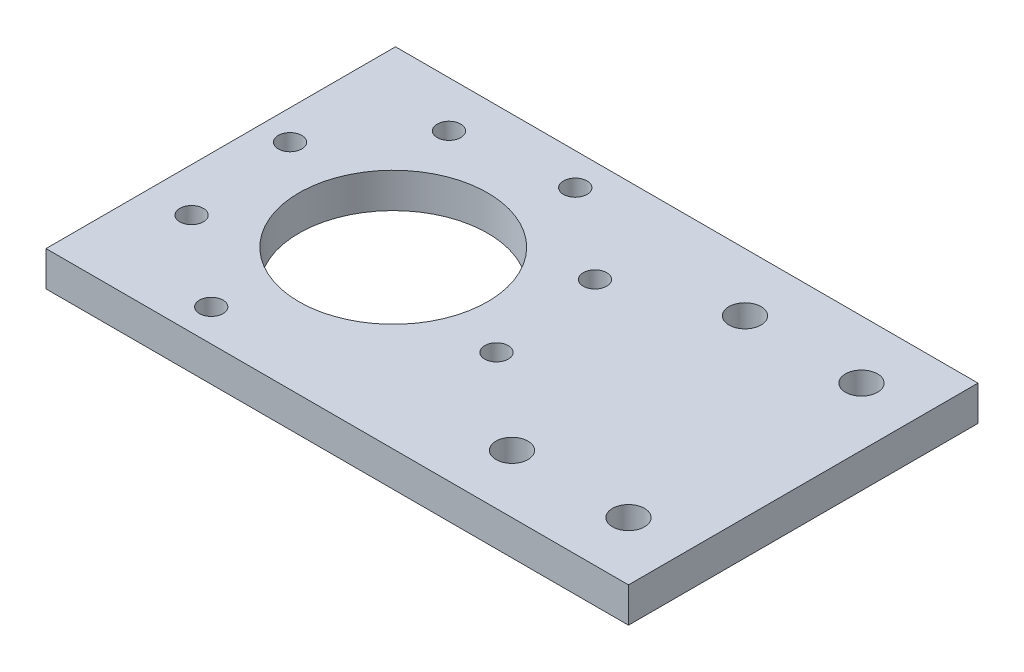
SolidWorks part; units mm, degrees
ref_plane "Front Plane" through (0, 0, 0) normal (0, 0, 1) x (1, 0, 0)
ref_plane "Top Plane" through (0, 0, 0) normal (0, 1, 0) x (1, 0, 0)
ref_plane "Right Plane" through (0, 0, 0) normal (1, 0, 0) x (0, 0, -1)
sketch "Sketch1" plane through (0, 0, 0) normal (0, 1, 0) x (1, 0, 0)
  line L1 (0, 0) -> (100, 0)
  line L2 (0, 0) -> (0, 60)
  line L3 (0, 60) -> (100, 60)
  line L4 (100, 0) -> (100, 60)
  dimension "D1" = 100
  dimension "D2" = 60
extrude "Boss-Extrude1" add sketch "Sketch1" along normal blind 6
sketch "Sketch2" plane through (0, 6, 0) normal (0, 1, 0) x (1, 0, 0)
  line L1 (100, 0) -> (100, 60) construction
  line L7 (100, 30) -> (0, 30) construction
  line L8 (0, 60) -> (0, 0) construction
  circle A0 centre (29.6153, 30) radius 16.1973
  circle A5 centre (70, 50) radius 2.75
  circle A6 centre (90, 50) radius 2.75
  circle A7 centre (70, 10) radius 2.75
  circle A8 centre (90, 10) radius 2.75
  point P7 (100, 30)
extrude "Cut-Extrude1" cut sketch "Sketch2" against normal blind 6
sketch "Sketch3" plane through (0, 0, 0) normal (0, -1, 0) x (1, 0, 0)
  circle A0 centre (54.0983, -23.2366) radius 2.0193 construction
  circle A1 centre (51.7099, -42.5296) radius 2.0193 construction
  circle A2 centre (36.3788, -54.483) radius 2.0193 construction
  circle A3 centre (17.0857, -52.0945) radius 2.0193 construction
  circle A4 centre (7.5208, -17.4704) radius 2.0193 construction
  circle A5 centre (22.8519, -5.517) radius 2.0193 construction
  circle A6 centre (54.0983, -23.2366) radius 2.0193
  circle A7 centre (51.7099, -42.5296) radius 2.0193
  circle A8 centre (36.3788, -54.483) radius 2.0193
  circle A9 centre (17.0857, -52.0945) radius 2.0193
  circle A10 centre (7.5208, -17.4704) radius 2.0193
  circle A11 centre (22.8519, -5.517) radius 2.0193
  circle A12 centre (5.1324, -36.7634) radius 2.0193 construction
  circle A13 centre (5.1324, -36.7634) radius 2.0193
extrude "Cut-Extrude2" cut sketch "Sketch3" against normal blind 6
